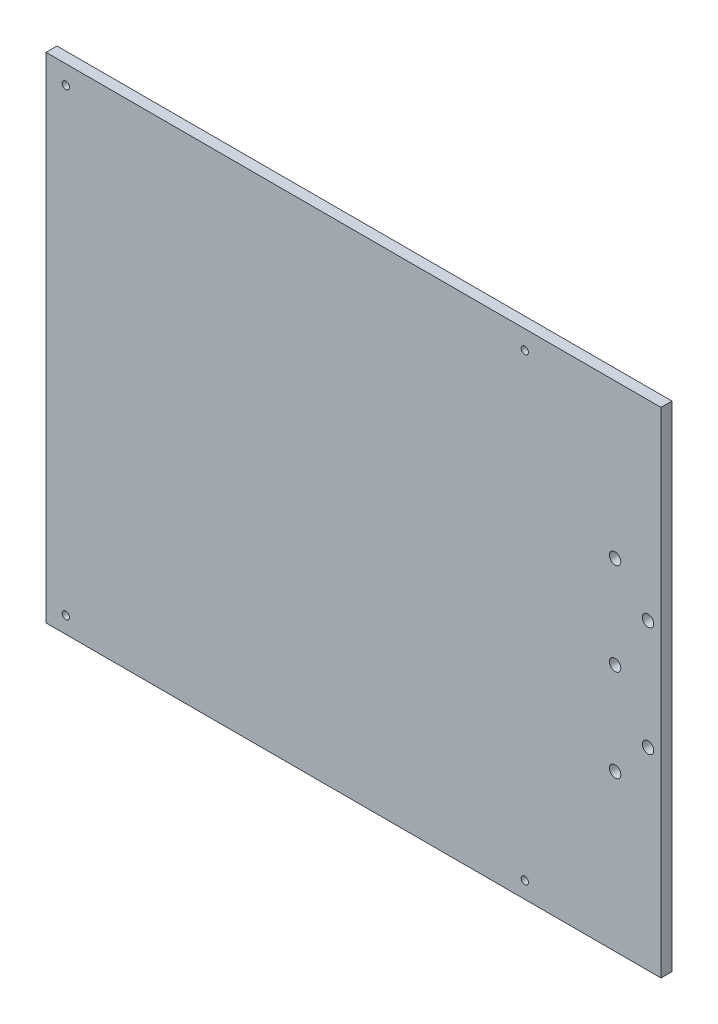
SolidWorks part; units mm, degrees
material "Lega 1060"
ref_plane "Piano frontale" through (0, 0, 0) normal (0, 0, 1) x (1, 0, 0)
ref_plane "Piano superiore" through (0, 0, 0) normal (0, 1, 0) x (1, 0, 0)
ref_plane "Piano destro" through (0, 0, 0) normal (1, 0, 0) x (0, 0, -1)
sketch "Schizzo1" plane through (0, 0, 0) normal (0, 0, 1) x (1, 0, 0)
  line L1 (0, 20) -> (-280, 20)
  line L2 (0, 20) -> (0, 245)
  line L3 (0, 245) -> (-280, 245)
  line L4 (-280, 20) -> (-280, 245)
  dimension "D1" = 280
  dimension "D2" = 225
  dimension "D3" = 20
extrude "Estrusione-Estrusione1" add sketch "Schizzo1" along normal blind 5
hole_wizard "Foro filettato M4-1" positions "Schizzo11" profile "Schizzo10" tap size "M4" standard "ISO" end condition up to next
sketch "Schizzo11" plane through (0, 0, 0) normal (0, 0, -1) x (-1, 0, 0)
  line L0 (280, 20) -> (0, 20) construction
  point P0 (271, 27.5)
  point P2 (62, 27.5)
  point P4 (271, 236.5)
  point P6 (62, 236.5)
  dimension "D1" = 7.5
  dimension "D2" = 209
  dimension "D3" = 209
  dimension "D4" = 9
sketch "Schizzo10" plane through (-271, 27.5, 0) normal (1, 0, 0) x (0, 1, 0)
  line L0 (0, 0) -> (0, 5)
  line L1 (0, 5) -> (1.65, 5)
  line L2 (1.65, 5) -> (1.65, 0)
  line L5 (1.65, 0) -> (0, 0)
  line L11 (0, -6.35) -> (0, 107.95) construction
  dimension "Thru Tap Drill Dia." = 3.3
  dimension "Thru Tap Drill Depth" = 5
cosmetic thread "Filettatura del foro2" parameters "D2"=4
cosmetic thread "Filettatura del foro4" parameters "D2"=4
cosmetic thread "Filettatura del foro5" parameters "D2"=4
cosmetic thread "Filettatura del foro6" parameters "D2"=4
sketch "Schizzo12" plane through (0, 0, 0) normal (0, 0, -1) x (-1, 0, 0)
  line L0 (0, 20) -> (0, 245) construction
  circle A0 centre (5.8957, 107.9884) radius 2.6
  circle A1 centre (5.8957, 157.9884) radius 2.6
  circle A2 centre (20.8957, 90.9884) radius 2.6
  circle A3 centre (20.8957, 132.9884) radius 2.6
  circle A4 centre (20.8957, 174.9884) radius 2.6
  dimension "D1" = 50
  dimension "D2" = 84
  dimension "D3" = 5.8957
  dimension "D4" = 20.8957
extrude "Taglio-Estrusione1" cut sketch "Schizzo12" against normal blind 10
